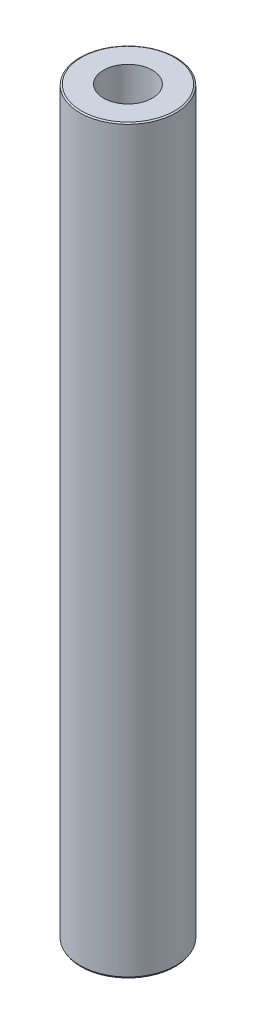
SolidWorks part; units mm, degrees
ref_plane "Front Plane" through (0, 0, 0) normal (0, 0, 1) x (1, 0, 0)
ref_plane "Top Plane" through (0, 0, 0) normal (0, 1, 0) x (1, 0, 0)
ref_plane "Right Plane" through (0, 0, 0) normal (1, 0, 0) x (0, 0, -1)
sketch "Sketch1" plane through (0, 0, 0) normal (0, 1, 0) x (1, 0, 0)
  circle A0 centre (0, 0) radius 35
  dimension "SHAFT_OD" = 70
extrude "Boss-Extrude1" add sketch "Sketch1" along normal blind 540.4082
sketch "Sketch2" plane through (0, 0, 0) normal (0, 1, 0) x (1, 0, 0)
  circle A0 centre (0, 0) radius 17.7538
  dimension "BORE_D" = 35.5075
extrude "Cut-Extrude1" cut sketch "Sketch2" along normal through all
chamfer "Chamfer1" distance 0.6408 angle 60 2 edges at (0, 540.4082, 35) (0, 0, 35) first distance on face at (0, 540.4082, 35) first distance on face at (0, 0, 17.7538)
